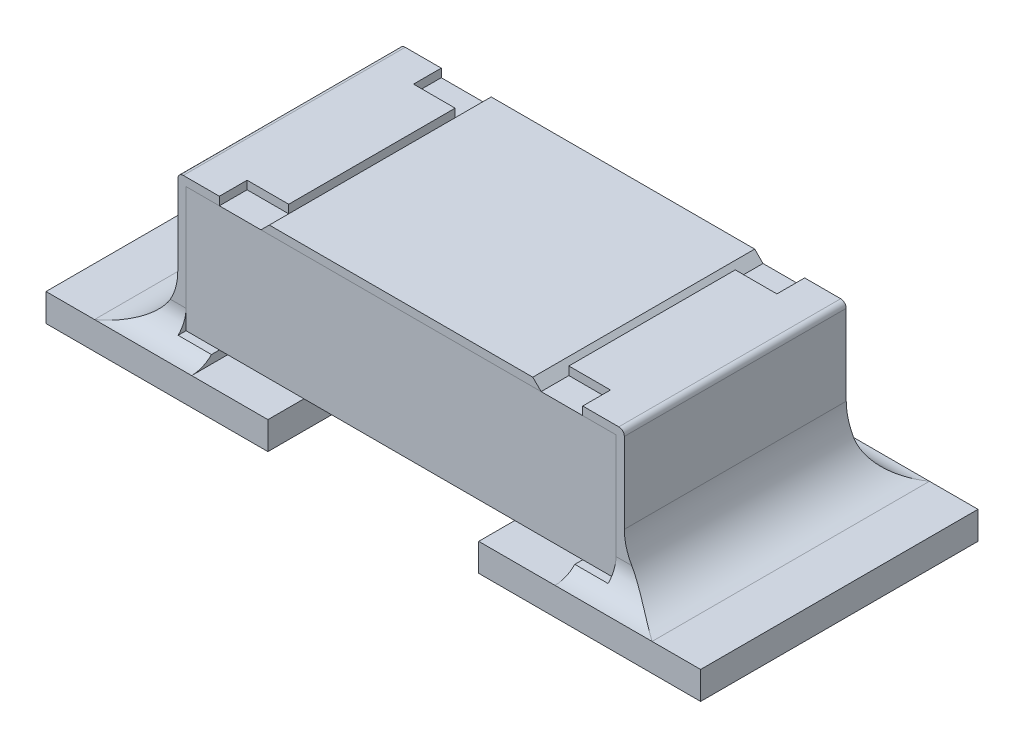
SolidWorks part; units mm, degrees
other "sopra"
other "base2"
other "base1"
other "corpo"
ref_plane "Front Plane" through (0, 0, 0) normal (0, 0, 1) x (1, 0, 0)
ref_plane "Top Plane" through (0, 0, 0) normal (0, 1, 0) x (1, 0, 0)
ref_plane "Right Plane" through (0, 0, 0) normal (1, 0, 0) x (0, 0, -1)
sketch "Sketch1" plane through (0, 0, 0) normal (1, 0, 0) x (0, 0, -1)
  line L1 (-0.4, 0.58) -> (0.4, 0.58)
  line L2 (-0.4, 0.58) -> (-0.4, 0.13)
  line L3 (-0.4, 0.13) -> (0.4, 0.13)
  line L4 (0.4, 0.58) -> (0.4, 0.13)
  line L5 (-0.4, 0.58) -> (0.4, 0.13) construction
  line L6 (-0.4, 0.13) -> (0.4, 0.58) construction
  point P0 (0, 0.355)
  point P5 (0, 0)
  dimension "D1" = 0.8
  dimension "D2" = 0.45
  dimension "D3" = 0.13
extrude "Boss-Extrude1" add sketch "Sketch1" along normal blind 1.55
sketch "Sketch2" plane through (0, 0, 0.4) normal (0, 0, 1) x (1, 0, 0)
  line L0 (0.27, 0.58) -> (0, 0.58)
  line L1 (0, 0.58) -> (0, 0.13)
  line L2 (0, 0.13) -> (0.27, 0.13)
  line L3 (0.775, 0.58) -> (0.775, 0.13) construction
  line L4 (1.55, 0.58) -> (0, 0.58) construction
  line L5 (1.55, 0.13) -> (0, 0.13) construction
  line L6 (0, 0.58) -> (0, 0.13) construction
  line L7 (0.27, 0.61) -> (-0.03, 0.61)
  line L8 (-0.03, 0.61) -> (-0.03, 0.1)
  line L9 (-0.03, 0.1) -> (0.27, 0.1)
  line L10 (0.27, 0.58) -> (0.27, 0.61)
  line L11 (0.27, 0.13) -> (0.27, 0.1)
  line L12 (1.28, 0.13) -> (1.28, 0.1)
  line L13 (1.28, 0.58) -> (1.28, 0.61)
  line L14 (1.58, 0.1) -> (1.28, 0.1)
  line L15 (1.58, 0.61) -> (1.58, 0.1)
  line L16 (1.28, 0.61) -> (1.58, 0.61)
  line L17 (1.55, 0.13) -> (1.28, 0.13)
  line L18 (1.55, 0.58) -> (1.55, 0.13)
  line L19 (1.28, 0.58) -> (1.55, 0.58)
  dimension "D1" = 0.27
  dimension "D2" = 0.03
extrude "Boss-Extrude2" add sketch "Sketch2" against normal up to surface (0.8 mm away) separate body up to face at (0.775, 0.355, -0.4)
fillet "Fillet1" radius 0.02 1 edges at (1.58, 0.61, 0)
fillet "Fillet2" radius 0.02 1 edges at (-0.03, 0.61, 0)
sketch "Sketch3" plane through (0, 0.61, 0) normal (0, 1, 0) x (1, 0, 0)
  line L0 (-0.01, 0.4) -> (0.27, 0.4) construction
  line L1 (0.12, 0.4) -> (0.27, 0.4)
  line L2 (0.12, 0.4) -> (0.12, 0.3)
  line L3 (0.12, 0.3) -> (0.27, 0.3)
  line L4 (0.27, 0.4) -> (0.27, 0.3)
  line L5 (0.12, 0.4) -> (0.27, 0.3) construction
  line L6 (0.12, 0.3) -> (0.27, 0.4) construction
  line L7 (0.27, 0.4) -> (0.27, -0.4) construction
  line L8 (0.775, 0.4) -> (0.775, -0.4) construction
  line L9 (1.55, 0.4) -> (0, 0.4) construction
  line L10 (1.55, -0.4) -> (0, -0.4) construction
  line L11 (1.56, 0) -> (-0.01, 0) construction
  line L12 (1.56, -0.4) -> (1.56, 0.4) construction
  line L13 (-0.01, 0.4) -> (-0.01, -0.4) construction
  line L14 (1.43, 0.4) -> (1.43, 0.3)
  line L15 (1.43, 0.4) -> (1.28, 0.4)
  line L16 (1.28, 0.4) -> (1.28, 0.3)
  line L17 (1.43, 0.3) -> (1.28, 0.3)
  line L18 (1.43, -0.4) -> (1.43, -0.3)
  line L19 (1.43, -0.4) -> (1.28, -0.4)
  line L20 (1.43, -0.3) -> (1.28, -0.3)
  line L21 (1.28, -0.4) -> (1.28, -0.3)
  line L22 (0.12, -0.4) -> (0.12, -0.3)
  line L23 (0.12, -0.4) -> (0.27, -0.4)
  line L24 (0.27, -0.4) -> (0.27, -0.3)
  line L25 (0.12, -0.3) -> (0.27, -0.3)
  point P0 (0.195, 0.35)
  dimension "D1" = 0.15
  dimension "D2" = 0.1
extrude "Cut-Extrude1" cut sketch "Sketch3" against normal through all
sketch "Sketch4" plane through (0, 0, 0.4) normal (0, 0, 1) x (1, 0, 0)
  line L0 (0.27, 0.58) -> (1.28, 0.58)
  line L1 (0.27, 0.58) -> (0.27, 0.61) construction
  line L2 (1.28, 0.58) -> (1.28, 0.61) construction
  line L3 (1.55, 0.58) -> (0, 0.58) construction
  line L4 (0.27, 0.58) -> (0.3, 0.61)
  line L5 (0.3, 0.61) -> (1.25, 0.61)
  line L6 (1.25, 0.61) -> (1.28, 0.58)
  line L8 (1.43, 0.61) -> (1.28, 0.61) construction
  point P2 (0.5877, 0.8609)
  point P10 (0.979, 0.8576)
  point P12 (0.775, 0.61)
  point P13 (0.775, 0.58)
  point P14 (1.061, 0.7242)
  dimension "D1" = 45
extrude "Boss-Extrude3" add sketch "Sketch4" against normal up to surface (0.8 mm away) separate body up to face at (0.775, 0.355, -0.4)
sketch "Sketch5" plane through (0, 0.1, 0) normal (0, -1, 0) x (1, 0, 0)
  line L0 (0, 0) -> (50000, 0) construction
  line L1 (0.775, 0.4) -> (0.775, -49999.6) construction
  line L2 (-0.405, 0.5) -> (0.395, 0.5)
  line L3 (-0.405, 0.5) -> (-0.405, -0.5)
  line L4 (-0.405, -0.5) -> (0.395, -0.5)
  line L5 (0.395, 0.5) -> (0.395, -0.5)
  line L6 (-0.405, 0.5) -> (0.395, -0.5) construction
  line L7 (-0.405, -0.5) -> (0.395, 0.5) construction
  line L8 (1.155, 0.5) -> (1.955, 0.5)
  line L9 (1.155, 0.5) -> (1.155, -0.5)
  line L10 (1.155, -0.5) -> (1.955, -0.5)
  line L11 (1.955, 0.5) -> (1.955, -0.5)
  line L12 (1.155, 0.5) -> (1.955, -0.5) construction
  line L13 (1.155, -0.5) -> (1.955, 0.5) construction
  line L14 (1.55, 0.4) -> (0, 0.4) construction
  point P3 (-0.005, 0)
  point P8 (1.555, 0)
  point P17 (0.775, 0.4)
  point P18 (0.1152, 0)
  point P19 (0.5982, -0.5)
  dimension "D1" = 0.8
  dimension "D2" = 1
  dimension "D3" = 0.38
extrude "Boss-Extrude4" add sketch "Sketch5" along normal blind 0.1
fillet "Fillet3" radius 0.2 1 edges at (-0.03, 0.1, 0)
fillet "Fillet4" radius 0.2 1 edges at (1.58, 0.1, 0)
fillet "Fillet5" radius 0.1 2 edges at (-0.055, 0.1, -0.4) (-0.055, 0.1, 0.4)
fillet "Fillet6" radius 0.1 2 edges at (1.605, 0.1, -0.4) (1.605, 0.1, 0.4)
